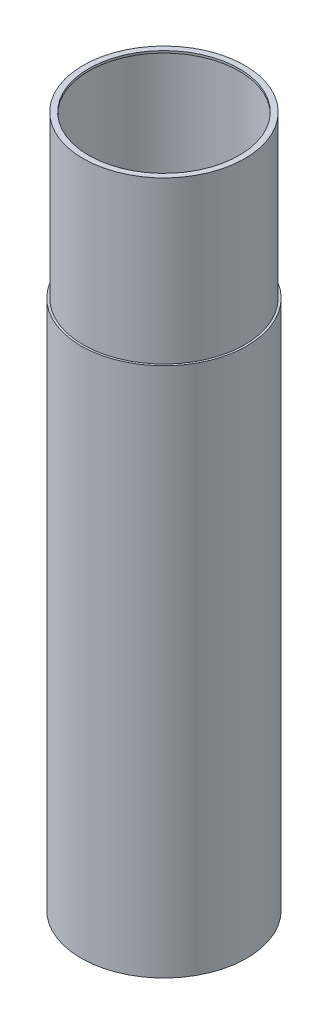
SolidWorks part; units mm, degrees
material "A-Glass Fiber"
ref_plane "Front Plane" through (0, 0, 0) normal (0, 0, 1) x (1, 0, 0)
ref_plane "Top Plane" through (0, 0, 0) normal (0, 1, 0) x (1, 0, 0)
ref_plane "Right Plane" through (0, 0, 0) normal (1, 0, 0) x (0, 0, -1)
sketch "Sketch1" plane through (0, 0, 0) normal (0, 0, 1) x (1, 0, 0)
  line L0 (78.16, 0) -> (78.16, 500)
  line L1 (76.2, 0) -> (76.2, 500)
  line L2 (78.16, 500) -> (76.2, 500)
  line L3 (76.2, 0) -> (78.16, 0)
  line L4 (0, 204.6154) -> (0, 85.8935) construction
  dimension "D1" = 76.2
  dimension "D2" = 500
  dimension "D3" = 1.96
revolve "Revolve1" add sketch "Sketch1" angle 360 about L4
sketch "Sketch3" plane through (0, 500, 0) normal (0, 1, 0) x (1, 0, 0)
  circle A2 centre (0, 0) radius 76.2 construction
  circle A3 centre (0, 0) radius 76.2
  circle A4 centre (0, 0) radius 75.2
  dimension "D1" = 1
extrude "Boss-Extrude1" add sketch "Sketch3" along normal blind 152 and the other way blind 152
sketch "Sketch4" plane through (0, 652, 0) normal (0, 1, 0) x (1, 0, 0)
  circle A0 centre (0, 0) radius 76.2
  circle A1 centre (0, 0) radius 70.915
extrude "Boss-Extrude2" add sketch "Sketch4" against normal blind 2
